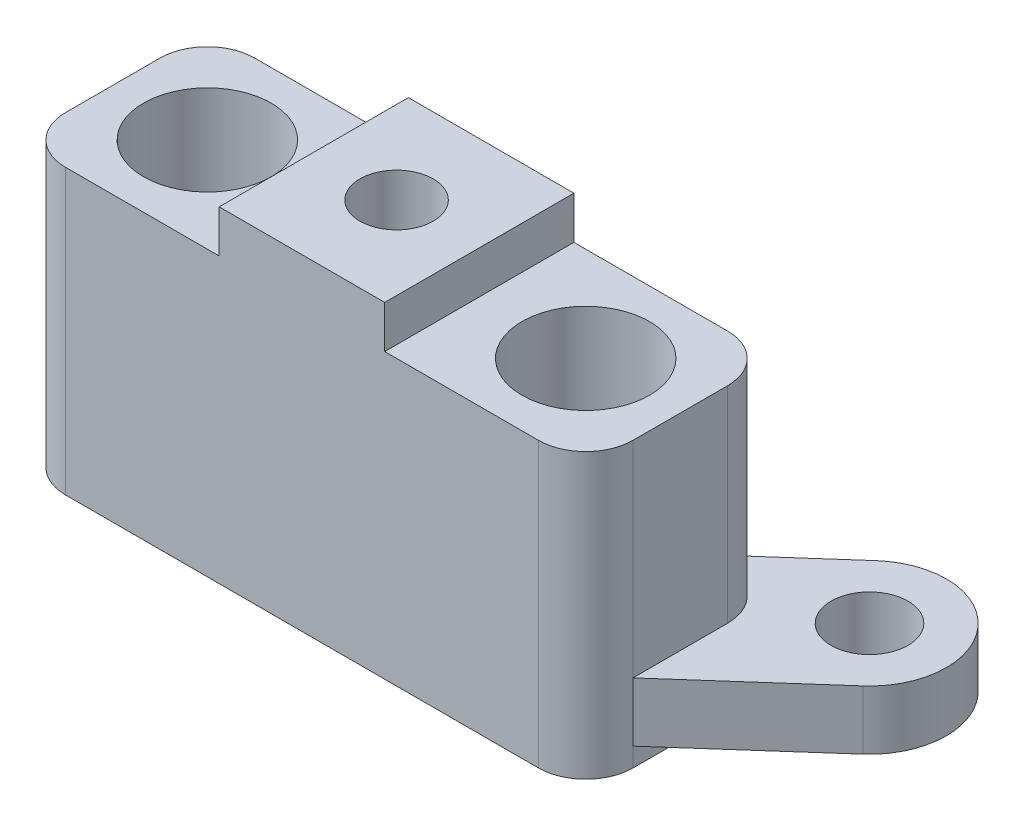
SolidWorks part; units mm, degrees
ref_plane "Front Plane" through (0, 0, 0) normal (0, 0, 1) x (1, 0, 0)
ref_plane "Top Plane" through (0, 0, 0) normal (0, 1, 0) x (1, 0, 0)
ref_plane "Right Plane" through (0, 0, 0) normal (1, 0, 0) x (0, 0, -1)
ref_axis "X-Axis" through (-88.4377, 0, 0) along (1, 0, 0)
ref_axis "Y-Axis" through (0, 0, -69.2525) along (0, 0, 1)
ref_axis "Z-Axis" through (0, -52.5493, 0) along (0, 1, 0)
sketch "Sketch25" plane through (0, 0, 0) normal (0, 1, 0) x (-1, 0, 0)
  line L8 (3.5, -4) -> (-3.5, -4)
  line L9 (3.5, -4) -> (3.5, 4)
  line L10 (3.5, 4) -> (-3.5, 4)
  line L11 (-3.5, -4) -> (-3.5, 4)
  line L12 (3.5, -4) -> (-3.5, 4) construction
  line L13 (3.5, 4) -> (-3.5, -4) construction
  point P8 (0, 0)
  dimension "D3" = 7
  dimension "D1" = 8
extrude "Boss-Extrude5" add sketch "Sketch25" along normal blind 13.8
sketch "Sketch26" plane through (0, 0, 0) normal (0, 1, 0) x (-1, 0, 0)
  line L0 (0, 4) -> (0, -4) construction
  line L1 (-12, -4) -> (12, -4)
  line L2 (-12, -4) -> (-12, 4)
  line L3 (-12, 4) -> (12, 4)
  line L4 (12, -4) -> (12, 4)
  line L5 (-12, 0) -> (12, 0) construction
  line L6 (-8, 0) -> (0, -4) construction
  line L7 (0, -4) -> (8, 0) construction
  line L10 (-3.5, -4) -> (3.5, -4) construction
  line L11 (3.5, 4) -> (-3.5, 4) construction
  circle A0 centre (-8, 0) radius 2.7
  circle A1 centre (8, 0) radius 2.7
  dimension "D2" = 5.4
  dimension "D1" = 24
  dimension "D3" = 16
extrude "Boss-Extrude6" add sketch "Sketch26" along normal blind 12
fillet "Fillet1" radius 2 4 edges at (12, 6, -4) (-12, 6, -4) (-12, 6, 4) (12, 6, 4)
sketch "Sketch27" plane through (0, 13.8, 0) normal (0, 1, 0) x (1, 0, 0)
  circle A0 centre (0, 0) radius 1.55
  dimension "D1" = 3.1
extrude "Cut-Extrude1" cut sketch "Sketch27" against normal blind 6.5
ref_plane "Plane1" through (0, 0.8, 0) normal (0, -1, 0) x (-1, 0, 0)
sketch "Sketch29" plane through (0, 0.8, 0) normal (0, -1, 0) x (1, 0, 0)
  line L0 (0, 0) -> (0, 33) construction
  line L1 (0, 33) -> (-15, 33) construction
  line L2 (-15, 33) -> (-15, -5) construction
  line L3 (-17.1552, -2.5674) -> (-12, 2)
  line L4 (-12.8448, -7.4326) -> (-8.9704, -4)
  line L5 (10, -4) -> (-10, -4) construction
  line L6 (-12, 2) -> (-11, -3)
  line L7 (-11, -3) -> (-8.9704, -4)
  line L8 (17.1552, -2.5674) -> (12, 2)
  line L9 (12, 2) -> (11, -3)
  line L10 (11, -3) -> (8.9704, -4)
  line L11 (12.8448, -7.4326) -> (8.9704, -4)
  circle A0 centre (-15, -5) radius 1.625
  arc A1 (-17.1552, -2.5674) -> (-12.8448, -7.4326) centre (-15, -5) ccw
  circle A2 centre (15, -5) radius 1.625
  arc A3 (17.1552, -2.5674) -> (12.8448, -7.4326) centre (15, -5) cw
  dimension "D4" = 3.25
  dimension "D5" = 6.5
  dimension "D1" = 33
  dimension "D2" = 38
  dimension "D3" = 15
extrude "Boss-Extrude8" add sketch "Sketch29" against normal blind 2.5
